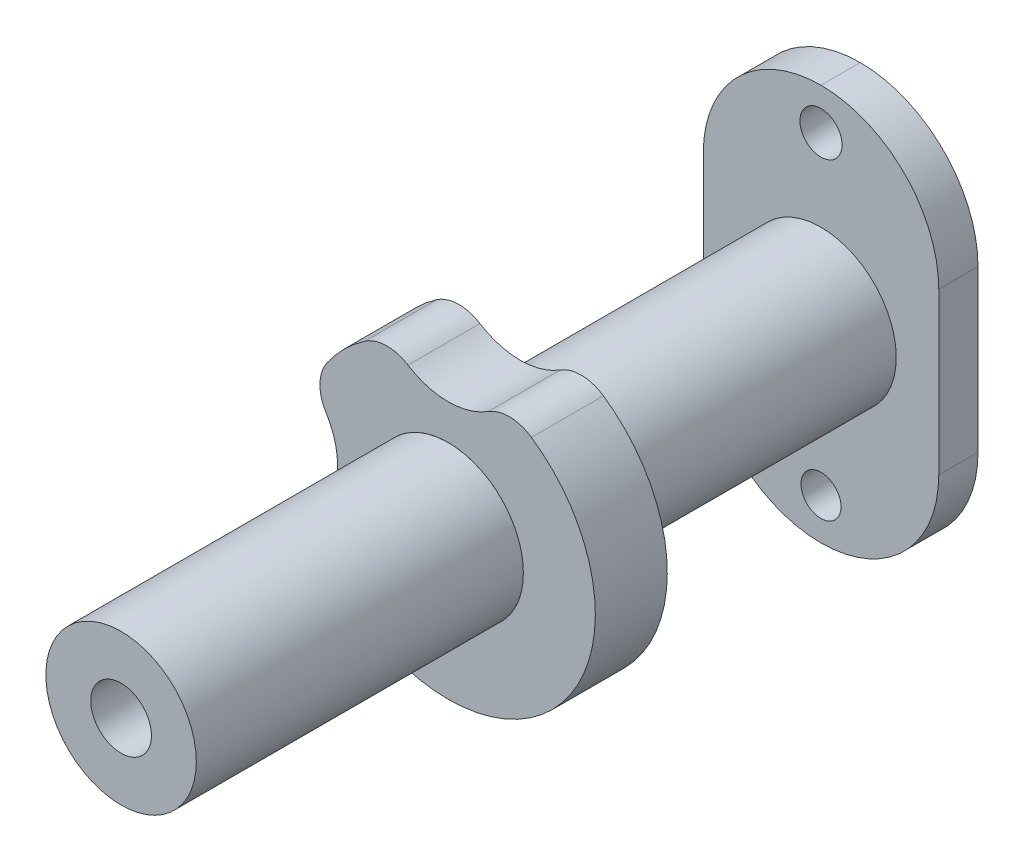
SolidWorks part; units mm, degrees
ref_plane "Alzado" through (0, 0, 0) normal (0, 0, 1) x (1, 0, 0)
ref_plane "Planta" through (0, 0, 0) normal (0, 1, 0) x (1, 0, 0)
ref_plane "Vista lateral" through (0, 0, 0) normal (1, 0, 0) x (0, 0, -1)
sketch "Croquis4" plane through (0, 0, 0) normal (0, 0, 1) x (1, 0, 0)
  circle A0 centre (0, 0) radius 5.75
  dimension "D1" = 11.5
extrude "Saliente-Extruir3" add sketch "Croquis4" along normal blind 15.5
sketch "Croquis5" plane through (0, 0, 0) normal (0, 0, -1) x (-1, 0, 0)
  circle A0 centre (0, 0) radius 11.25
  dimension "D1" = 22.5
extrude "Saliente-Extruir4" add sketch "Croquis5" against normal blind 5.5
sketch "Croquis7" plane through (0, 0, 0) normal (0, 0, -1) x (-1, 0, 0)
  circle A0 centre (0, 0) radius 2.32
  dimension "D1" = 4.64
extrude "Cortar-Extruir2" cut sketch "Croquis7" against normal blind 25.5
sketch "Croquis8" plane through (0, 0, 0) normal (0, 0, -1) x (-1, 0, 0)
  circle A0 centre (0, 0) radius 5.75
  dimension "D1" = 11.5
extrude "Saliente-Extruir5" add sketch "Croquis8" along normal blind 12.7
sketch "Croquis9" plane through (0, 0, -12.7) normal (0, 0, -1) x (-1, 0, 0)
  line L1 (9, 15.15) -> (-9, 15.15)
  line L2 (9, 15.15) -> (9, -15.15)
  line L3 (9, -15.15) -> (-9, -15.15)
  line L4 (-9, 15.15) -> (-9, -15.15)
  line L5 (9, 15.15) -> (-9, -15.15) construction
  line L6 (9, -15.15) -> (-9, 15.15) construction
  point P0 (0, 0)
  dimension "D1" = 18
  dimension "D2" = 30.3
extrude "Saliente-Extruir6" add sketch "Croquis9" against normal blind 3
sketch "Croquis10" plane through (0, 0, 15.5) normal (0, 0, 1) x (1, 0, 0)
  circle A0 centre (0, 0) radius 2.32
extrude "Cortar-Extruir3" cut sketch "Croquis10" against normal blind 53
fillet "Redondeo5" radius 9 4 edges at (9, -15.15, -11.2) (-9, -15.15, -11.2) (-9, 15.15, -11.2) (9, 15.15, -11.2)
sketch "Croquis14" plane through (0, 0, -12.7) normal (0, 0, -1) x (-1, 0, 0)
  circle A0 centre (0, 12) radius 1.6104
  circle A1 centre (0, -12) radius 1.53
  dimension "D3" = 3.2209
  dimension "D4" = 3.06
  dimension "D1" = 12
  dimension "D2" = 12
extrude "Cortar-Extruir4" cut sketch "Croquis14" against normal blind 10
sketch "Croquis15" plane through (0, 0, 15.5) normal (0, 0, 1) x (1, 0, 0)
  circle A0 centre (0, 0) radius 2.32 construction
  circle A1 centre (0, 0) radius 5.75
  circle A2 centre (0, 0) radius 5.75
  circle A3 centre (0, 0) radius 2.32
  dimension "D1" = 0
extrude "Saliente-Extruir8" add sketch "Croquis15" along normal blind 3 contours A3 | A2
sketch "Croquis16" plane through (0, 0, -9.7) normal (0, 0, 1) x (1, 0, 0)
  line L2 (9, -6.15) -> (9, 6.15)
  line L3 (-9, 6.15) -> (-9, -6.15)
  line L4 (9, -6.15) -> (9, 6.15)
  line L5 (-9, 6.15) -> (-9, -6.15)
  circle A0 centre (0, 12) radius 1.6104 construction
  circle A1 centre (0, 12) radius 1.6104
  circle A2 centre (0, -12) radius 1.53 construction
  circle A3 centre (0, -12) radius 1.53
  arc A4 (-9, -6.15) -> (0, -15.15) centre (0, -6.15) ccw
  arc A5 (0, -15.15) -> (9, -6.15) centre (0, -6.15) ccw
  arc A6 (9, 6.15) -> (0, 15.15) centre (0, 6.15) ccw
  arc A7 (0, 15.15) -> (-9, 6.15) centre (0, 6.15) ccw
  arc A8 (-9, -6.15) -> (0, -15.15) centre (0, -6.15) ccw
  arc A9 (0, -15.15) -> (9, -6.15) centre (0, -6.15) ccw
  arc A10 (9, 6.15) -> (0, 15.15) centre (0, 6.15) ccw
  arc A11 (0, 15.15) -> (-9, 6.15) centre (0, 6.15) ccw
  circle A13 centre (0, 0) radius 5.75
  circle A14 centre (0, 0) radius 5.75
  dimension "D1" = 0
  dimension "D2" = 0
sketch "Croquis18" plane through (0, 0, 0) normal (1, 0, 0) x (0, 0, -1)
sketch "Croquis22" plane through (0, 0, 5.5) normal (0, 0, 1) x (1, 0, 0)
  circle A1 centre (0, 0) radius 11.25
  circle A2 centre (0, 0) radius 11.25
  dimension "D1" = 0
extrude "Saliente-Extruir10" add sketch "Croquis22" along normal blind 10 contours A2
sketch "Croquis24" plane through (0, 0, -9.7) normal (0, 0, 1) x (1, 0, 0)
  circle A0 centre (0, 0) radius 5.75 construction
  circle A1 centre (0, 0) radius 5.75
  circle A2 centre (0, 0) radius 23.7653
extrude "Cortar-Extruir7" cut sketch "Croquis24" along normal blind 22.5
sketch "Croquis25" plane through (0, 0, 12.8) normal (0, 0, -1) x (-1, 0, 0)
  circle A1 centre (0, 0) radius 11.25
  circle A2 centre (0, 0) radius 11.25
  dimension "D1" = 0
extrude "Saliente-Extruir11" add sketch "Croquis25" against normal blind 5.5
sketch "Croquis27" plane through (0, 0, 12.8) normal (0, 0, -1) x (-1, 0, 0)
  circle A0 centre (0, 0) radius 5.75 construction
  circle A1 centre (0, 0) radius 11.25
  circle A2 centre (0, 0) radius 11.25
  circle A3 centre (0, 0) radius 5.75
  dimension "D1" = 0
extrude "Cortar-Extruir10" cut sketch "Croquis27" against normal blind 0.5 contours A2 | A3
sketch "Croquis28" plane through (0, 0, 18.5) normal (0, 0, 1) x (1, 0, 0)
  circle A1 centre (0, 0) radius 5.75
  circle A2 centre (0, 0) radius 5.75
  dimension "D1" = 0
sketch "Croquis29" plane through (0, 0, 13.3) normal (0, 0, -1) x (-1, 0, 0)
  circle A0 centre (0, 0) radius 5.75 construction
  circle A1 centre (0, 0) radius 11.25
  circle A2 centre (0, 0) radius 11.25
  circle A3 centre (0, 0) radius 5.75
  dimension "D1" = 0
extrude "Saliente-Extruir12" add sketch "Croquis29" against normal blind 5.5
sketch "Croquis30" plane through (0, 0, 18.8) normal (0, 0, 1) x (1, 0, 0)
  circle A0 centre (0, 0) radius 5.75 construction
  circle A1 centre (0, 0) radius 5.75
extrude "Saliente-Extruir13" add sketch "Croquis30" along normal blind 25 separate body
sketch "Croquis31" plane through (0, 0, -12.7) normal (0, 0, -1) x (-1, 0, 0)
  circle A0 centre (0, 0) radius 2.32 construction
  circle A1 centre (0, 0) radius 2.32
extrude "Cortar-Extruir11" cut sketch "Croquis31" against normal blind 105
sketch "Croquis32" plane through (0, 0, 18.8) normal (0, 0, 1) x (1, 0, 0)
  line L0 (11.25, 0) -> (-10.15, 0) construction
  line L1 (0, -11.25) -> (0, 10.15) construction
  line L2 (0, 10.15) -> (-10.15, 10.15) construction
  line L3 (-10.15, 10.15) -> (-10.15, 0) construction
  circle A0 centre (0, 0) radius 11.25 construction
  circle A2 centre (-14.2, 0) radius 5.75
  circle A3 centre (0, 14.2) radius 5.75
  dimension "D3" = 11.5
  dimension "D4" = 11.5
  dimension "D1" = 21.4
  dimension "D2" = 21.4
  dimension "D5" = 14.2
  dimension "D6" = 14.2
extrude "Cortar-Extruir12" cut sketch "Croquis32" against normal blind 10
fillet "Redondeo6" radius 3 4 edges at (-10.3923, -4.3085, 16.05) (-10.3923, 4.3085, 16.05) (4.3085, 10.3923, 16.05) (-4.3085, 10.3923, 16.05)
